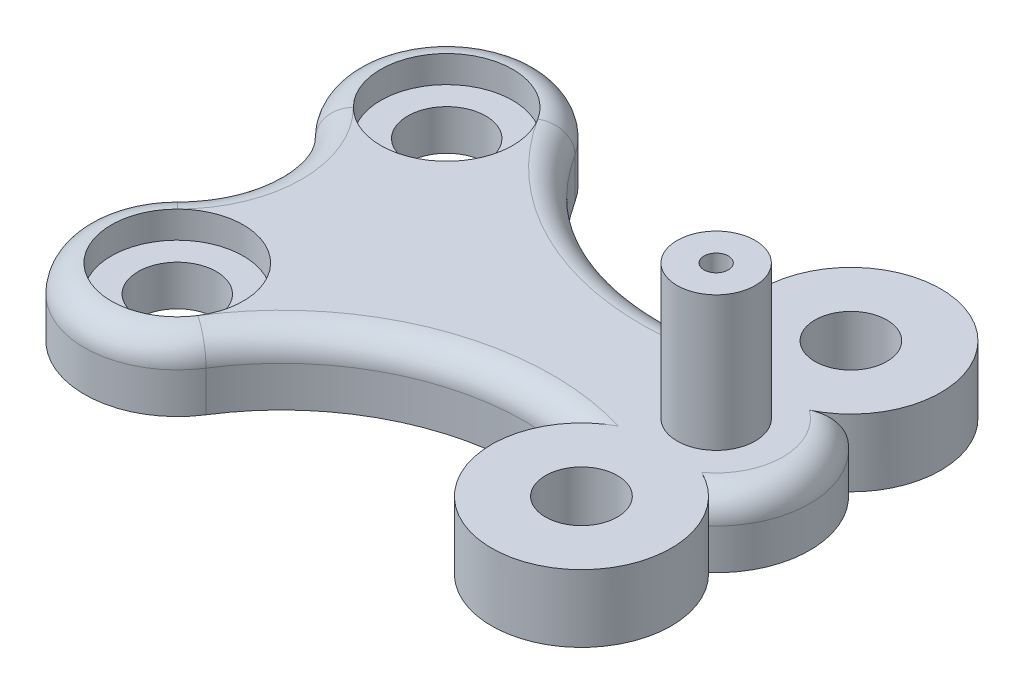
SolidWorks part; units mm, degrees
ref_plane "Alzado" through (0, 0, 0) normal (0, 0, 1) x (1, 0, 0)
ref_plane "Planta" through (0, 0, 0) normal (0, 1, 0) x (1, 0, 0)
ref_plane "Vista lateral" through (0, 0, 0) normal (1, 0, 0) x (0, 0, -1)
sketch "Croquis2" plane through (0, 0, 0) normal (0, 1, 0) x (1, 0, 0)
  line L0 (-5, 0) -> (15, 0) construction
  line L1 (7.5, 1.2807) -> (7.5, -1.2409) construction
  line L2 (0, 5) -> (15, 0) construction
  line L3 (15, 0) -> (0, -5) construction
  line L4 (7.5, 2.5) -> (9.1667, 7.5) construction
  line L5 (7.5, -2.5) -> (10.8333, -12.5) construction
  line L6 (9.1667, 7.5) -> (16.6667, 5) construction
  line L7 (9.1667, 7.5) -> (1.6667, 10) construction
  line L8 (0, 5) -> (3.6431, 15.9293) construction
  line L9 (15, 0) -> (16.6667, 5) construction
  line L10 (0, 5) -> (20.1884, 5) construction
  line L11 (0, -5) -> (20.1884, -5) construction
  circle A0 centre (0, 5) radius 1.45
  circle A1 centre (0, -5) radius 1.45
  circle A2 centre (15, 0) radius 1.475 construction
  arc A3 (17.3112, -2.595) -> (17.3112, 2.595) centre (15, 0) ccw
  arc A4 (2.9139, 6.847) -> (-2.4395, 2.5605) centre (0, 5) ccw
  arc A5 (2.9139, -6.847) -> (-2.4395, -2.5605) centre (0, -5) cw
  arc A6 (-2.4395, -2.5605) -> (-2.4395, 2.5605) centre (-5, 0) ccw
  arc A8 (2.9139, 6.847) -> (12.4601, 2.838) centre (10.5657, 11.6971) ccw
  arc A9 (2.9139, -6.847) -> (12.4601, -2.838) centre (10.5657, -11.6971) cw
  circle A10 centre (15, -5) radius 1.3355
  circle A11 centre (0, 5) radius 3.45 construction
  circle A12 centre (0, -5) radius 3.45 construction
  circle A13 centre (15, 0) radius 3.475 construction
  circle A14 centre (15, 5) radius 1.3355
  arc A15 (12.4601, -2.838) -> (17.3112, -2.595) centre (15, -5) ccw
  arc A16 (12.4601, 2.838) -> (17.3112, 2.595) centre (15, 5) cw
  circle A18 centre (15, 5) radius 3.3355 construction
  circle A19 centre (15, -5) radius 3.3355 construction
  point P13 (3.45, -5)
  point P15 (18.3232, 1.016)
  point P32 (3.45, 5)
  point P44 (18.3355, -5)
  point P45 (18.3355, 5)
  dimension "D2" = 2.9
  dimension "D3" = 2.95
  dimension "D1" = 5
  dimension "D6" = 5
  dimension "D7" = 15
  dimension "D8" = 0
  dimension "D9" = 7.5
  dimension "D10" = 5
  dimension "D11" = 10
  dimension "D12" = 15
  dimension "D13" = 0
  dimension "D14" = 15
  dimension "D4" = 2
  dimension "D5" = 2
  dimension "D15" = 2
extrude "Saliente-Extruir1" add sketch "Croquis2" along normal blind 2.5
sketch "Croquis3" plane through (0, 2.5, 0) normal (0, 1, 0) x (1, 0, 0)
  circle A2 centre (0, 5) radius 2.45
  circle A3 centre (0, 5) radius 2.45
  circle A5 centre (0, -5) radius 2.45
  circle A6 centre (0, -5) radius 2.45
  dimension "D1" = 1
  dimension "D2" = 1
extrude "Cortar-Extruir1" cut sketch "Croquis3" against normal blind 1
sketch "Croquis4" plane through (0, 2.5, 0) normal (0, 1, 0) x (1, 0, 0)
  circle A0 centre (15, 0) radius 1.45
  circle A1 centre (15, 0) radius 0.45
  dimension "D1" = 2.9
  dimension "D2" = 1
extrude "Saliente-Extruir2" add sketch "Croquis4" along normal blind 5
sketch "Croquis5" plane through (0, 2.5, 0) normal (0, 1, 0) x (1, 0, 0)
  circle A1 centre (15, 0) radius 0.45
  circle A2 centre (15, 0) radius 0.45
  dimension "D1" = 0
extrude "Cortar-Extruir2" cut sketch "Croquis5" against normal through all
fillet "Redondeo1" radius 1 6 edges at (7.0579, 2.5, -3.3444) (-2.1564, 2.5, -7.6931) (7.0579, 2.5, 3.3444) (18.475, 2.5, 0) (-2.1564, 2.5, 7.6931) (-1.3789, 2.5, 0)
